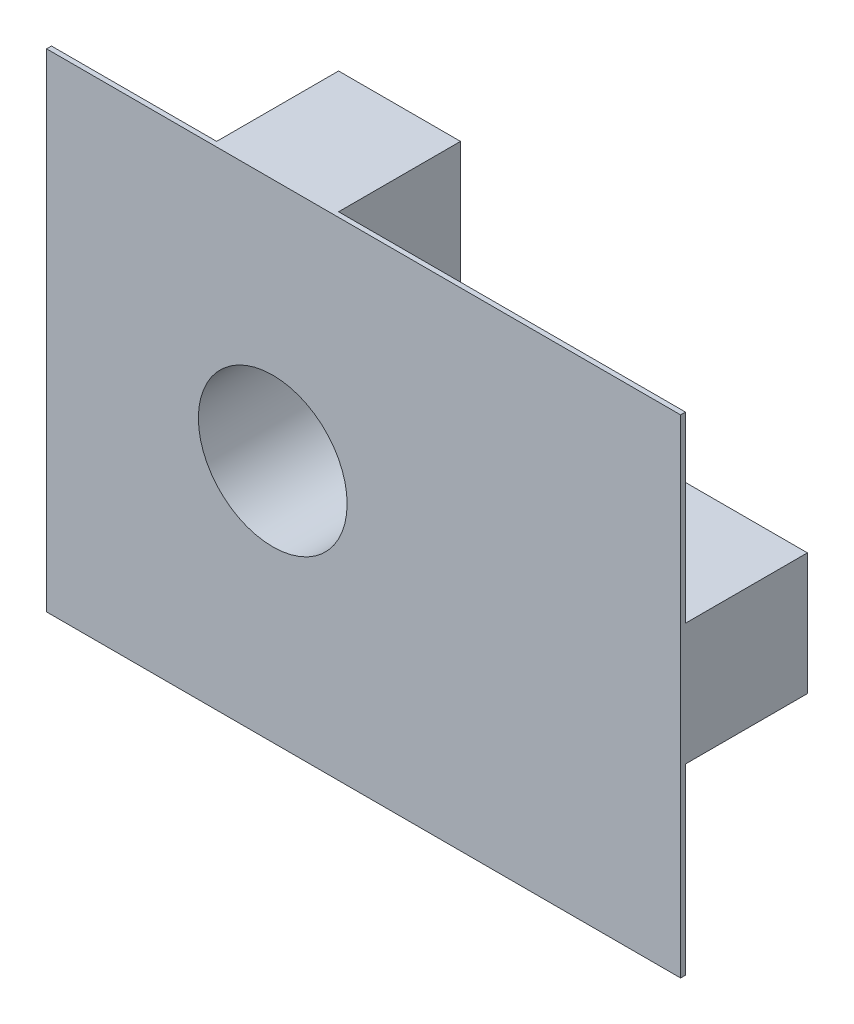
SolidWorks part; units mm, degrees
ref_plane "Спереди" through (0, 0, 0) normal (0, 0, 1) x (1, 0, 0)
ref_plane "Сверху" through (0, 0, 0) normal (0, 1, 0) x (1, 0, 0)
ref_plane "Справа" through (0, 0, 0) normal (1, 0, 0) x (0, 0, -1)
other "Configuration Table"
sketch "Эскиз1" plane through (0, 0, 0) normal (0, 0, 1) x (1, 0, 0)
  line L1 (130, 100) -> (-130, 100)
  line L2 (130, 100) -> (130, -100)
  line L3 (130, -100) -> (-130, -100)
  line L4 (-130, 100) -> (-130, -100)
  line L5 (130, 100) -> (-130, -100) construction
  line L6 (130, -100) -> (-130, 100) construction
  circle A0 centre (-37.26, 0) radius 30.5
  point P0 (0, 0)
  dimension "D3" = 61
  dimension "D1" = 260
  dimension "D2" = 200
  dimension "D4" = 92.74
extrude "Бобышка-Вытянуть1" add sketch "Эскиз1" along normal blind 2
sketch "Эскиз2" plane through (0, 0, 0) normal (0, 0, -1) x (-1, 0, 0)
  line L0 (-130, 100) -> (130, 100) construction
  line L5 (-130, -100) -> (-130, 100) construction
  line L6 (-130, 25) -> (19.7886, 25)
  line L7 (-130, 25) -> (-130, -25)
  line L8 (-130, -25) -> (19.7886, -25)
  line L9 (19.7886, 25) -> (19.7886, -25)
  line L10 (12.26, 100) -> (62.26, 100)
  line L11 (12.26, 100) -> (12.26, 17.4714)
  line L12 (12.26, 17.4714) -> (62.26, 17.4714) construction
  line L13 (62.26, 100) -> (62.26, 17.4714)
  line L14 (6.76, 0) -> (67.76, 0) construction
  line L15 (37.26, 30.5) -> (37.26, -30.5) construction
  line L16 (12.26, -100) -> (62.26, -100)
  line L17 (62.26, -100) -> (62.26, -17.4714)
  line L18 (12.26, -100) -> (12.26, -17.4714)
  line L19 (130, 100) -> (130, -100) construction
  line L20 (54.7314, 25) -> (130, 25)
  line L21 (54.7314, 25) -> (54.7314, -25)
  line L22 (54.7314, -25) -> (130, -25)
  line L23 (130, 25) -> (130, -25)
  circle A0 centre (37.26, 0) radius 30.5
  circle A1 centre (37.26, 0) radius 30.5 construction
  point P9 (-130, 0)
  point P17 (37.26, 100)
  point P32 (130, 0)
  point P35 (0, 0)
  line M12 (130, -100) -> (130, 100)
  line M13 (130, 100) -> (-130, 100)
  line M14 (-130, 100) -> (-130, -100)
  line M15 (-130, -100) -> (130, -100)
  circle M16 centre (37.26, 0) radius 30.5
  dimension "D1" = 50
  dimension "D3" = 50
  dimension "D2" = 50
extrude "Бобышка-Вытянуть5" add sketch "Эскиз2" along normal blind 50 contours L18 L8 M16 | L22 L17 M16 | L20 L13 M16 | L6 L11 M16 | L20 L13 L11 L6 M16 M13 | L8 L18 L11 L6 M16 M14 | L22 L8 L18 L17 M16 M15 | L17 L22 L20 L13 M12 M16 region at (60.1592, 0, 0) region at (-37.26, 63.7734, 0) region at (-14.6202, 22.6398, 0) region at (-14.6202, -22.6398, 0) region at (-37.26, -63.7734, 0) region at (-59.8998, 22.6398, 0) region at (-59.8998, -22.6398, 0) region at (-97.3997, 0, 0)
equation "\"D3@Эскиз2\"=\"D1@Эскиз2\""
equation "\"D2@Эскиз2\"=\"D1@Эскиз2\""
